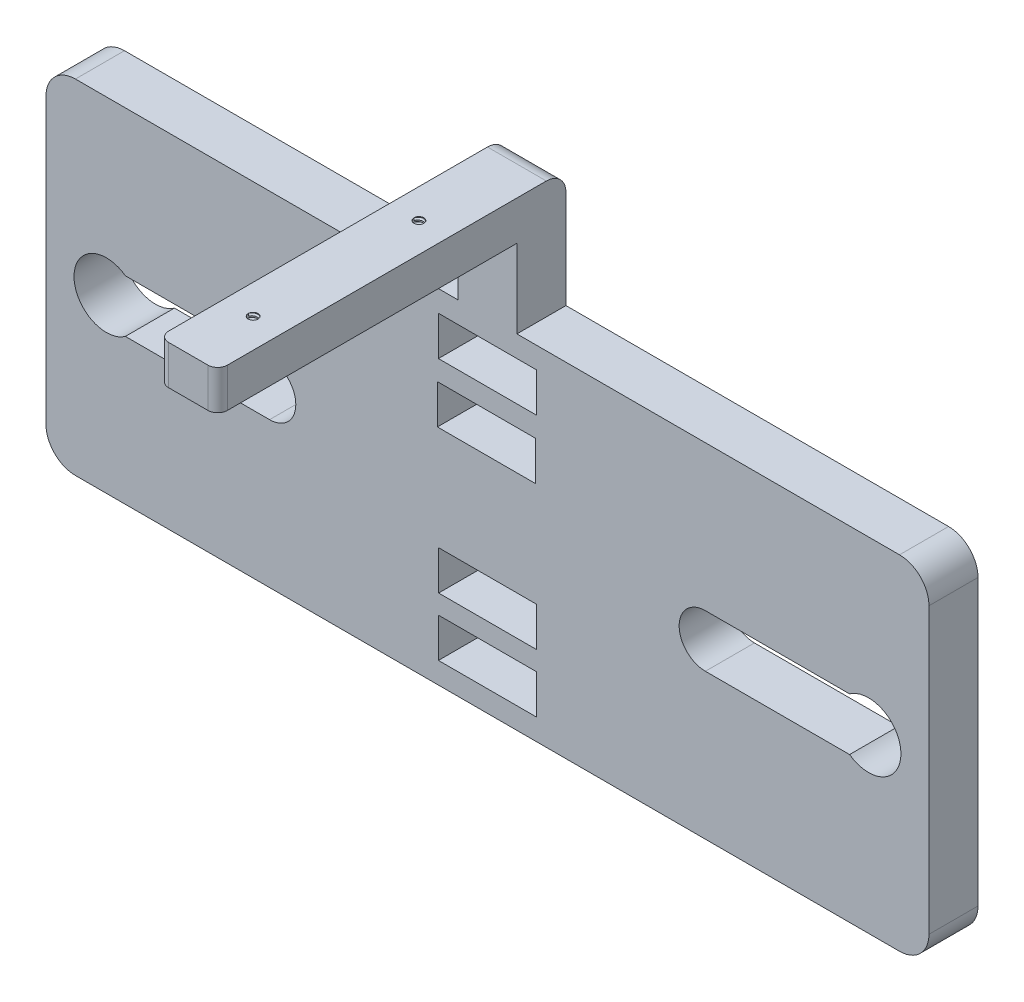
SolidWorks part; units mm, degrees
ref_plane "Front Plane" through (0, 0, 0) normal (0, 0, 1) x (1, 0, 0)
ref_plane "Top Plane" through (0, 0, 0) normal (0, 1, 0) x (1, 0, 0)
ref_plane "Right Plane" through (0, 0, 0) normal (1, 0, 0) x (0, 0, -1)
sketch "Sketch1" plane through (0, 0, 0) normal (0, 0, 1) x (1, 0, 0)
  line L12 (0, 0) -> (56.8962, 0)
  line L13 (56.8962, 0) -> (56.8962, 35)
  line L14 (56.8962, 35) -> (-33.1038, 35)
  line L15 (-33.1038, 35) -> (-33.1038, 0)
  line L16 (-33.1038, 0) -> (0, 0)
  line L17 (-33.1038, 17.5) -> (63.2462, 17.5) construction
  line L18 (-25.2981, 17.5) -> (-10.3153, 17.5) construction
  line L19 (-25.2981, 20.175) -> (-10.3153, 20.175)
  line L20 (-25.2981, 14.825) -> (-10.3153, 14.825)
  line L21 (11.8962, 35) -> (11.8962, 0) construction
  line L22 (49.0906, 17.5) -> (34.1077, 17.5) construction
  line L23 (49.0906, 20.175) -> (34.1077, 20.175)
  line L24 (49.0906, 14.825) -> (34.1077, 14.825)
  line L25 (6.8962, 6.1763) -> (16.8962, 6.1763)
  line L26 (16.8962, 6.1763) -> (16.8962, 2.1763)
  line L27 (16.8962, 2.1763) -> (6.8962, 2.1763)
  line L28 (6.8962, 6.1763) -> (6.8962, 2.1763)
  line L29 (16.8962, 28.8237) -> (16.8962, 32.8237)
  line L30 (6.8962, 28.8237) -> (16.8962, 28.8237)
  line L31 (6.8962, 28.8237) -> (6.8962, 32.8237)
  line L32 (16.8962, 32.8237) -> (6.8962, 32.8237)
  line L33 (6.9174, 12.136) -> (16.9174, 12.136)
  line L34 (16.9174, 12.136) -> (16.9174, 8.136)
  line L35 (16.9174, 8.136) -> (6.9174, 8.136)
  line L36 (6.9174, 12.136) -> (6.9174, 8.136)
  line L37 (6.7926, 26.7349) -> (16.7926, 26.7349)
  line L38 (16.7926, 26.7349) -> (16.7926, 22.7349)
  line L39 (16.7926, 22.7349) -> (6.7926, 22.7349)
  line L40 (6.7926, 26.7349) -> (6.7926, 22.7349)
  circle A0 centre (-26.9472, 17.5) radius 3.3
  arc A1 (-25.2981, 20.175) -> (-25.2981, 14.825) centre (-25.2981, 17.5) ccw
  arc A2 (-10.3153, 14.825) -> (-10.3153, 20.175) centre (-10.3153, 17.5) ccw
  circle A3 centre (50.7397, 17.5) radius 3.3
  arc A4 (49.0906, 20.175) -> (49.0906, 14.825) centre (49.0906, 17.5) cw
  arc A5 (34.1077, 14.825) -> (34.1077, 20.175) centre (34.1077, 17.5) cw
  point P12 (-17.8067, 17.5)
  point P24 (41.5992, 17.5)
  point P31 (11.8962, 2.1763)
  point P34 (11.8962, 6.1763)
  point P40 (11.9174, 8.136)
  point P43 (11.9174, 12.136)
  point P46 (11.7926, 22.7349)
  point P49 (11.7926, 26.7349)
  dimension "D3" = 5
  dimension "D1" = 35
  dimension "D2" = 90
  dimension "D4" = 4
extrude "Boss-Extrude1" add sketch "Sketch1" along normal blind 5 contours L15 L16 L12 L13 L14 A2 L20 A0 L19 L32 L29 L30 L31 L28 L25 L26 L27 L24 A5 L23 A3 region at (11.8974, 17.5019, 0)
fillet "Fillet1" radius 3 4 edges at (56.8962, 35, 2.5) (56.8962, 0, 2.5) (-33.1038, 0, 2.5) (-33.1038, 35, 2.5)
sketch "Sketch9" plane through (0, 35, 0) normal (0, 1, 0) x (1, 0, 0)
  line L0 (11.8962, 0) -> (11.8962, -5) construction
  line L1 (53.8962, 0) -> (-30.1038, 0) construction
  line L2 (53.8962, -5) -> (-30.1038, -5) construction
  line L3 (8.8962, 0) -> (8.8962, -5)
  line L4 (8.8962, -5) -> (14.8962, -5)
  line L6 (14.8962, 0) -> (8.8962, 0)
  line L7 (14.8962, 0) -> (14.8962, -5)
  dimension "D1" = 3
extrude "Boss-Extrude3" add sketch "Sketch9" along normal blind 12
sketch "Sketch11" plane through (0, 0, 5) normal (0, 0, 1) x (1, 0, 0)
  line L0 (8.8962, 47) -> (14.8962, 47)
  line L1 (14.8962, 47) -> (14.8962, 43)
  line L2 (14.8962, 47) -> (14.8962, 35) construction
  line L3 (14.8962, 43) -> (8.8962, 43)
  line L4 (8.8962, 47) -> (8.8962, 35) construction
  line L5 (8.8962, 43) -> (8.8962, 47)
  dimension "D1" = 4
extrude "Boss-Extrude4" add sketch "Sketch11" along normal blind 30.5
sketch "Sketch12" plane through (0, 47, 0) normal (0, 1, 0) x (1, 0, 0)
  line L0 (11.8962, -35.5) -> (11.8962, 0) construction
  line L1 (14.8962, -35.5) -> (8.8962, -35.5) construction
  line L2 (14.8962, 0) -> (8.8962, 0) construction
  circle A0 centre (11.8962, -11.9843) radius 0.5
  circle A1 centre (11.8962, -28.8843) radius 0.5
  point P8 (11.8962, -23.6243)
  point P9 (11.8962, -23.9668)
  point P12 (11.8962, -24.1951)
  point P13 (11.8962, -23.9824)
  point P14 (11.8962, -10.2877)
  point P15 (11.8962, -11.9843)
  dimension "D1" = 16.9
extrude "Cut-Extrude2" cut sketch "Sketch12" against normal blind 10.5
thread "Thread3" pitch 0.35 method cut profile "Thread Profile3" start angle 0, offset 0, length 10, pitch 0.4, diameter 1
ref_plane "Plane3" through (11.3962, 47, 28.8843) normal (0, 0, 1) x (-1, 0, 0)
sketch "Thread Profile3" plane through (11.3962, 47, 28.8843) normal (0, 0, 1) x (-1, 0, 0)
  line L0 (0, 0) -> (0, 0.35) construction
  line L1 (0, 0) -> (0.1894, 0.1094)
  line L2 (0.1894, 0.1094) -> (0.1894, 0.1531)
  line L3 (0.1894, 0.1531) -> (0, 0.2625)
  line L4 (0.1894, 0.1312) -> (0, 0.1312) construction
  line L11 (0, 0) -> (0, 0.2625)
  point P2 (0, 0)
  dimension "Pitch" = 0.35
  dimension "Profile_Angle" = 60
  dimension "Profile_Land" = 0.0437
  dimension "Profile_Height" = 0.1894
thread "Thread4" pitch 0.35 method cut profile "Thread Profile4" start angle 0, offset 0, length 10, pitch 0.4, diameter 1
ref_plane "Plane4" through (11.3962, 47, 11.9843) normal (0, 0, 1) x (-1, 0, 0)
sketch "Thread Profile4" plane through (11.3962, 47, 11.9843) normal (0, 0, 1) x (-1, 0, 0)
  line L0 (0, 0) -> (0, 0.35) construction
  line L1 (0, 0) -> (0.1894, 0.1094)
  line L2 (0.1894, 0.1094) -> (0.1894, 0.1531)
  line L3 (0.1894, 0.1531) -> (0, 0.2625)
  line L4 (0.1894, 0.1312) -> (0, 0.1312) construction
  line L11 (0, 0) -> (0, 0.2625)
  point P2 (0, 0)
  dimension "Pitch" = 0.35
  dimension "Profile_Angle" = 60
  dimension "Profile_Land" = 0.0437
  dimension "Profile_Height" = 0.1894
fillet "Fillet3" radius 2 1 edges at (11.8962, 47, 0)
fillet "Fillet4" radius 1 2 edges at (14.8962, 45, 35.5) (8.8962, 45, 35.5)
